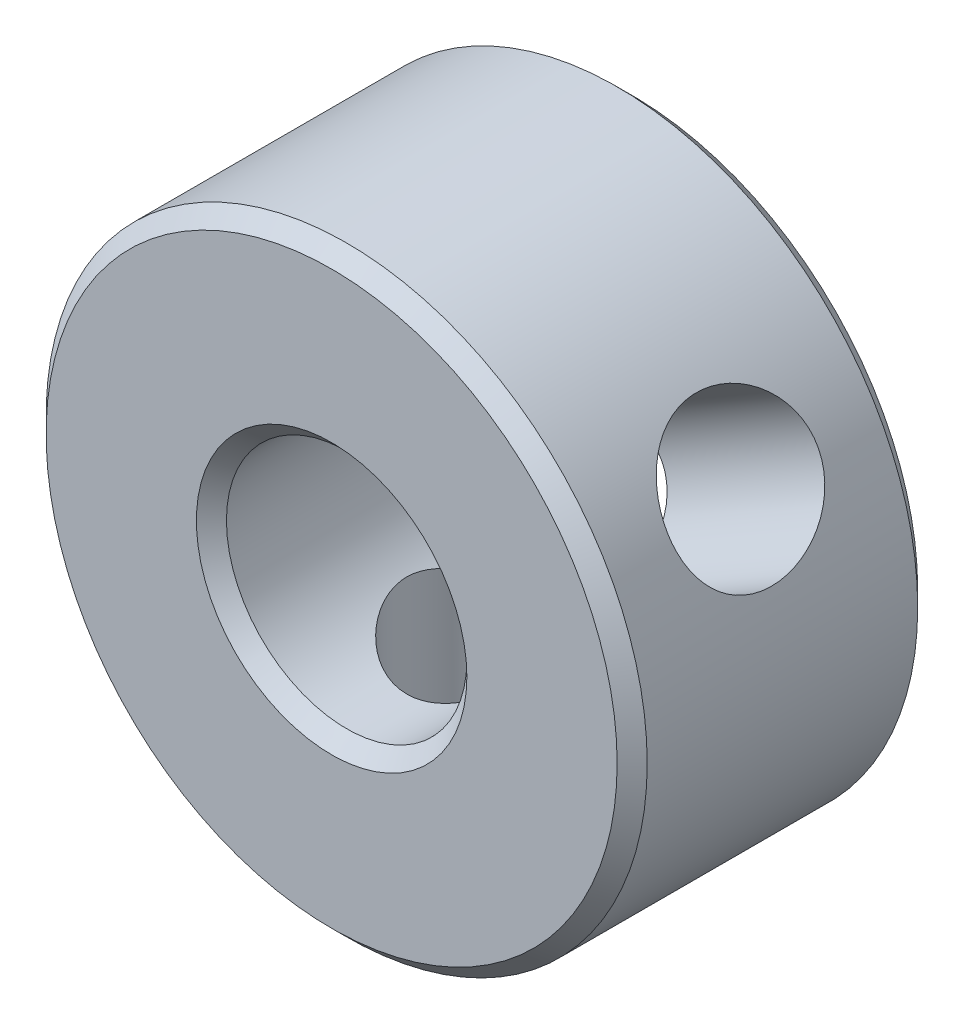
SolidWorks part; units mm, degrees
ref_plane "Front" through (0, 0, 0) normal (0, 0, 1) x (1, 0, 0)
ref_plane "Top" through (0, 0, 0) normal (0, 1, 0) x (1, 0, 0)
ref_plane "Right" through (0, 0, 0) normal (1, 0, 0) x (0, 0, -1)
sketch "Sketch1" plane through (0, 0, 0) normal (0, 0, 1) x (1, 0, 0)
  circle A0 centre (0, 0) radius 10
  circle A1 centre (0, 0) radius 4
  dimension "d" = 8
  dimension "D0" = 20
extrude "Base-Extrude" add sketch "Sketch1" against normal blind 10
chamfer "Chamfer1" distance 0.5 angle 45 2 edges at (10, 0, 0) (10, 0, -10)
sketch "Sketch2" plane through (0, 0, 0) normal (0, 1, 0) x (1, 0, 0)
  line L0 (9.5, 10) -> (-9.5, 10) construction
  line L1 (0, 3.5505) -> (0, -10.3547) construction
  circle A0 centre (0, 5) radius 2.5
  dimension "H/2" = 5
extrude "Hole" cut sketch "Sketch2" against normal through all
chamfer "EndChamfer" distance 0.5 angle 45 2 edges at (4, 0, -10) (4, 0, 0)
pattern_circular "HolePat" count 2 every 120 about axis through (0, 0, -10) along (0, 0, 1) of "Hole"
equation "\"H/2@Sketch2\" = \"H@Base-Extrude\" / 2"
